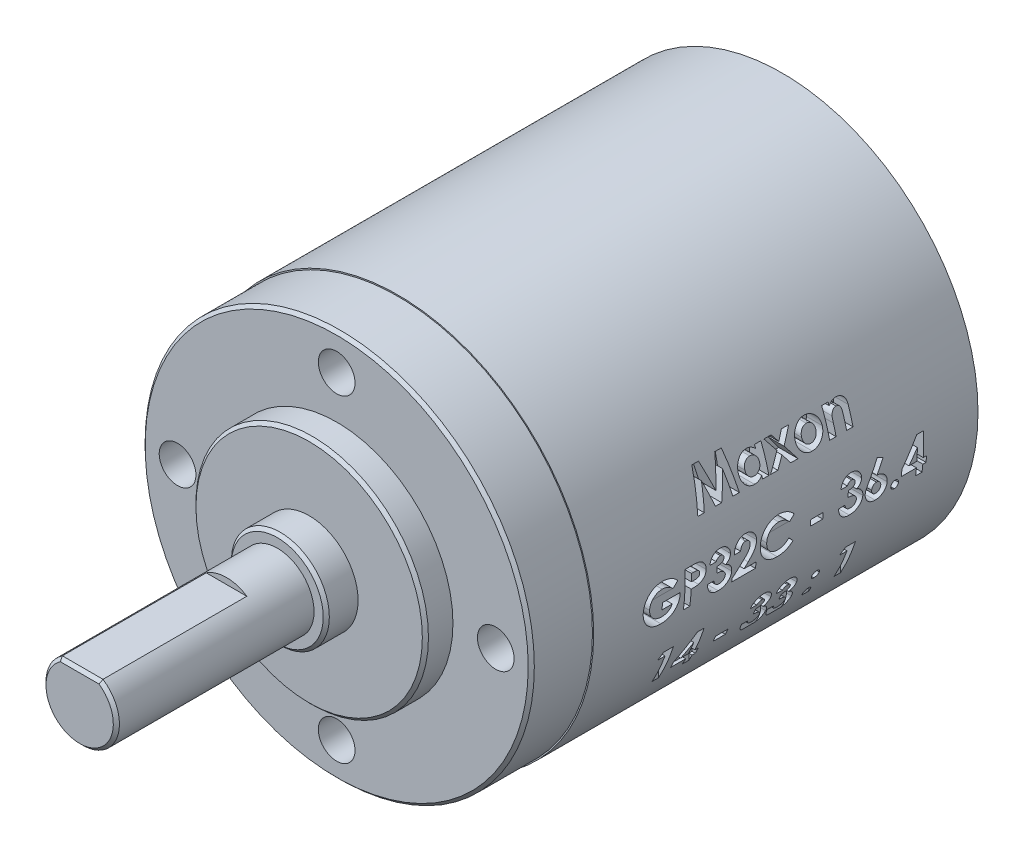
SolidWorks part; units mm, degrees
material "0.6015 (EN-GJL-150)"
ref_plane "Plan de face" through (0, 0, 0) normal (0, 0, 1) x (1, 0, 0)
ref_plane "Plan de dessus" through (0, 0, 0) normal (0, 1, 0) x (1, 0, 0)
ref_plane "Plan de droite" through (0, 0, 0) normal (1, 0, 0) x (0, 0, -1)
sketch "Esquisse1" plane through (0, 0, 0) normal (0, 0, 1) x (1, 0, 0)
  circle A0 centre (0, 0) radius 16
extrude "Boss.-Extru.1" add sketch "Esquisse1" along normal blind 36.4
sketch "Esquisse2" plane through (0, 0, 36.4) normal (0, 0, 1) x (1, 0, 0)
  circle A0 centre (0, 0) radius 9.5
extrude "Boss.-Extru.2" add sketch "Esquisse2" along normal blind 2.25
sketch "Esquisse3" plane through (0, 0, 38.65) normal (0, 0, 1) x (1, 0, 0)
  circle A0 centre (0, 0) radius 4
extrude "Boss.-Extru.3" add sketch "Esquisse3" along normal blind 2.6
sketch "Esquisse4" plane through (0, 0, 41.25) normal (0, 0, 1) x (1, 0, 0)
  circle A0 centre (0, 0) radius 3
extrude "Boss.-Extru.4" add sketch "Esquisse4" along normal blind 16.15
sketch "Esquisse5" plane through (0, 0, 36.4) normal (0, 0, 1) x (1, 0, 0)
  line L0 (0, 0) -> (0, 16) construction
  circle A0 centre (0, 0) radius 16 construction
  circle A1 centre (0, 13) radius 1.5
  circle A2 centre (13, 0) radius 1.5
  circle A3 centre (0, -13) radius 1.5
  circle A4 centre (-13, 0) radius 1.5
  dimension "D1" = 13
  dimension "D2" = 4
extrude "Enlèv. mat.-Extru.1" cut sketch "Esquisse5" against normal blind 3.8
sketch "Esquisse6" plane through (0, 0, 57.4) normal (0, 0, 1) x (1, 0, 0)
  line L0 (-1.6583, 2.5) -> (1.6583, 2.5)
  arc A0 (-1.6583, 2.5) -> (1.6583, 2.5) centre (0, 0) cw
  circle A1 centre (0, 0) radius 3 construction
  dimension "D1" = 2.5
extrude "Enlèv. mat.-Extru.2" cut sketch "Esquisse6" against normal blind 12
sketch "Esquisse7" plane through (0, 0, 36.4) normal (0, 0, 1) x (1, 0, 0)
  circle A0 centre (0, 0) radius 15.9
  circle A1 centre (0, 0) radius 16
  dimension "D1" = 31.8
extrude "Enlèv. mat.-Extru.3" cut sketch "Esquisse7" against normal blind 5
sketch "Esquisse8" plane through (0, 0, 0) normal (0, 0, -1) x (-1, 0, 0)
  circle A0 centre (0, 0) radius 10
extrude "Enlèv. mat.-Extru.4" cut sketch "Esquisse8" against normal blind 25
chamfer "Chanfrein1" distance 0.25 angle 45 5 edges at (0, 2.5, 57.4) (0, -3, 57.4) (15.9, 0, 36.4) (9.5, 0, 38.65) (4, 0, 41.25)
ref_plane "Plan1" through (16, 0, 0) normal (1, 0, 0) x (0, 0, -1)
sketch "Esquisse9" plane through (16, 0, 0) normal (1, 0, 0) x (0, 0, -1)
  text T0 "<b>     Maxon</b>\r\n<b>GP32C - 36.4</b>\r\n<b>  14 - 33 : 1</b>\r\n" font "Century Gothic" height in points 11
extrude "Enlèv. mat.-Extru.5" cut sketch "Esquisse9" against normal blind 2 body kept at (15.9, 0, 36.15)
